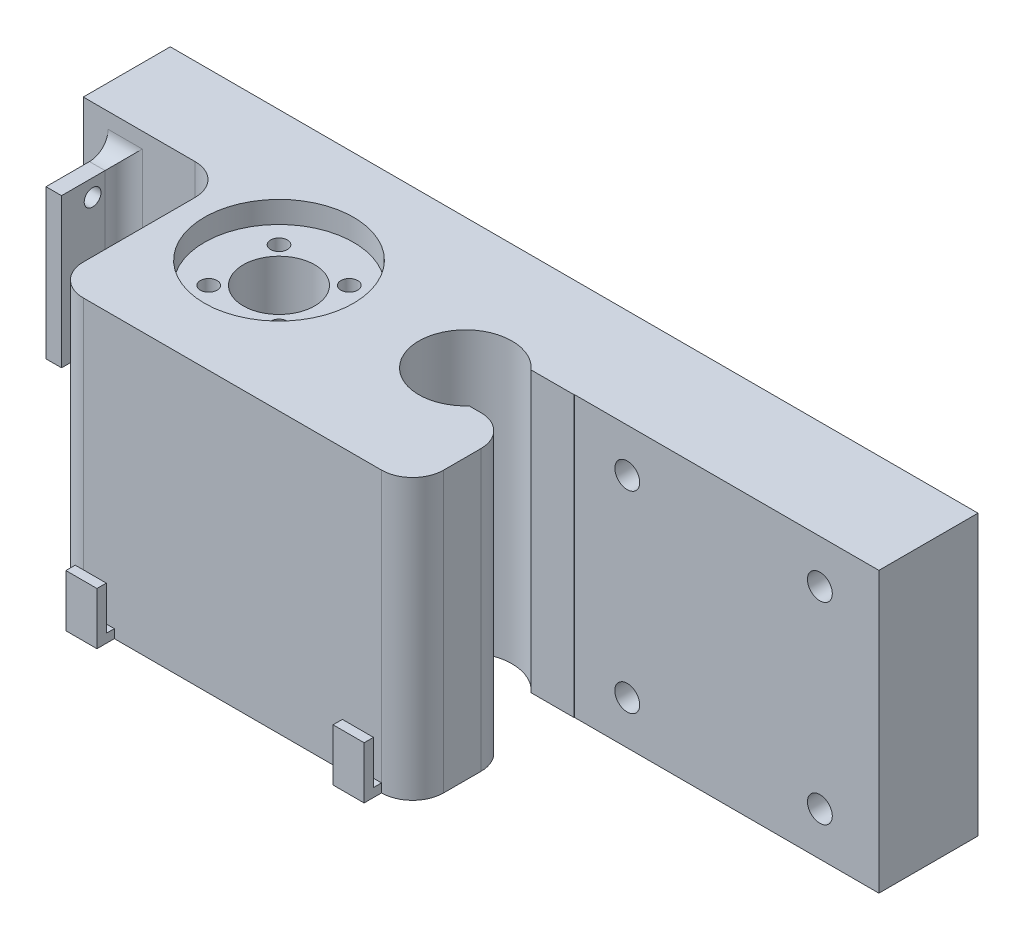
SolidWorks part; units mm, degrees
ref_plane "Front Plane" through (0, 0, 0) normal (0, 0, 1) x (1, 0, 0)
ref_plane "Top Plane" through (0, 0, 0) normal (0, 1, 0) x (1, 0, 0)
ref_plane "Right Plane" through (0, 0, 0) normal (1, 0, 0) x (0, 0, -1)
sketch "Sketch1" plane through (0, 0, 0) normal (0, 0, 1) x (1, 0, 0)
  line L1 (0, 0) -> (130, 0)
  line L2 (0, 0) -> (0, 45)
  line L3 (0, 45) -> (130, 45)
  line L4 (130, 0) -> (130, 45)
  dimension "D1" = 45
  dimension "D2" = 130
extrude "Boss-Extrude1" add sketch "Sketch1" along normal blind 42
sketch "Sketch2" plane through (0, 0, 0) normal (-1, 0, 0) x (0, 0, 1)
  line L0 (42, 22.5) -> (0, 22.5) construction
  line L5 (42, 45) -> (42, 0) construction
  line L6 (0, 45) -> (0, 0) construction
  line L8 (2, 12.5) -> (12, 12.5)
  line L9 (2, 12.5) -> (2, 32.5)
  line L10 (2, 32.5) -> (12, 32.5)
  line L11 (12, 12.5) -> (12, 32.5)
  line L12 (2, 12.5) -> (12, 32.5) construction
  line L13 (2, 32.5) -> (12, 12.5) construction
  point P10 (7, 22.5)
  dimension "D1" = 2
  dimension "D2" = 20
  dimension "D3" = 10
extrude "Cut-Extrude1" cut sketch "Sketch2" against normal blind 115
sketch "Sketch3" plane through (0, 0, 0) normal (0, 0, -1) x (-1, 0, 0)
  line L1 (-120.5, 38) -> (-89.5, 38) construction
  line L2 (-120.5, 38) -> (-120.5, 7) construction
  line L3 (-120.5, 7) -> (-89.5, 7) construction
  line L4 (-89.5, 38) -> (-89.5, 7) construction
  line L5 (-120.5, 38) -> (-89.5, 7) construction
  line L6 (-120.5, 7) -> (-89.5, 38) construction
  line L7 (-125.5, 43) -> (-84.5, 43)
  line L8 (-125.5, 43) -> (-125.5, 2)
  line L9 (-125.5, 2) -> (-84.5, 2)
  line L10 (-84.5, 43) -> (-84.5, 2)
  line L11 (-125.5, 43) -> (-84.5, 2) construction
  line L12 (-125.5, 2) -> (-84.5, 43) construction
  point P4 (-105, 22.5)
  point P11 (-105, 22.5)
  dimension "D1" = 5
  dimension "D2" = 5
extrude "Cut-Extrude2" cut sketch "Sketch3" against normal blind 12
sketch "Sketch5" plane through (0, 0, 42) normal (0, 0, 1) x (1, 0, 0)
  line L0 (0, 0) -> (130, 0) construction
  line L1 (130, 45) -> (81, 45)
  line L2 (130, 45) -> (130, 0)
  line L3 (130, 0) -> (81, 0)
  line L4 (81, 45) -> (81, 0)
  line L5 (130, 45) -> (81, 0) construction
  line L6 (130, 0) -> (81, 45) construction
  point P4 (105.5, 22.5)
  dimension "D1" = 49
extrude "Cut-Extrude3" cut sketch "Sketch5" against normal up to surface (26.05 mm away)
sketch "Sketch6" plane through (0, 0, 0) normal (0, 0, -1) x (-1, 0, 0)
  line L1 (-120.5, 38) -> (-89.5, 38) construction
  line L2 (-120.5, 38) -> (-120.5, 7) construction
  line L3 (-120.5, 7) -> (-89.5, 7) construction
  line L4 (-89.5, 38) -> (-89.5, 7) construction
  line L5 (-120.5, 38) -> (-89.5, 7) construction
  line L6 (-120.5, 7) -> (-89.5, 38) construction
  circle A0 centre (-120.5, 38) radius 2
  circle A1 centre (-89.5, 38) radius 2
  circle A2 centre (-89.5, 7) radius 2
  circle A3 centre (-120.5, 7) radius 2
  point P4 (-105, 22.5)
  dimension "D1" = 4
  dimension "D2" = 4
  dimension "D3" = 4
  dimension "D4" = 4
extrude "Cut-Extrude4" cut sketch "Sketch6" against normal through all
sketch "Sketch7" plane through (0, 45, 0) normal (0, 1, 0) x (1, 0, 0)
  circle A0 centre (38.5, -21) radius 12
  dimension "D1" = 24
extrude "Cut-Extrude5" cut sketch "Sketch7" against normal blind 3.5
sketch "Sketch8" plane through (0, 45, 0) normal (0, 1, 0) x (1, 0, 0)
  circle A0 centre (68.5, -21) radius 7.5
  dimension "D1" = 15
extrude "Cut-Extrude6" cut sketch "Sketch8" against normal through all
sketch "Sketch10" plane through (0, 45, 0) normal (0, 1, 0) x (1, 0, 0)
  line L1 (0, -42) -> (23, -42)
  line L2 (0, -42) -> (0, -14)
  line L3 (0, -14) -> (23, -14)
  line L4 (23, -42) -> (23, -14)
  line L5 (0, -42) -> (23, -14) construction
  line L6 (0, -14) -> (23, -42) construction
  point P4 (11.5, -28)
  dimension "D1" = 28
  dimension "D2" = 23
extrude "Cut-Extrude7" cut sketch "Sketch10" against normal through all
fillet "Fillet1" radius 5 2 edges at (23, 22.5, 42) (81, 22.5, 42)
sketch "Sketch11" plane through (0, 41.5, 0) normal (0, 1, 0) x (1, 0, 0)
  circle A0 centre (38.5, -21) radius 5.75
  dimension "D1" = 11.5
extrude "Cut-Extrude8" cut sketch "Sketch11" against normal through all
sketch "Sketch12" plane through (0, 41.5, 0) normal (0, 1, 0) x (1, 0, 0)
  circle A0 centre (32.8431, -15.3431) radius 1.35
  circle A1 centre (44.1569, -15.3431) radius 1.35
  circle A2 centre (44.1569, -26.6569) radius 1.35
  circle A3 centre (32.8431, -26.6569) radius 1.35
  dimension "D1" = 2.7
extrude "Cut-Extrude9" cut sketch "Sketch12" against normal blind 20
sketch "Sketch14" plane through (0, 0, 0) normal (0, 0, -1) x (-1, 0, 0)
  line L0 (0, 22.5) -> (-84.5, 22.5) construction
  line L1 (-75, 7.5) -> (-15, 7.5) construction
  line L2 (-75, 7.5) -> (-75, 37.5) construction
  line L3 (-75, 37.5) -> (-15, 37.5) construction
  line L4 (-15, 7.5) -> (-15, 37.5) construction
  line L5 (-75, 7.5) -> (-15, 37.5) construction
  line L6 (-75, 37.5) -> (-15, 7.5) construction
  line L7 (0, 45) -> (0, 0) construction
  line L8 (-84.5, 2) -> (-84.5, 43) construction
  circle A0 centre (-75, 37.5) radius 1.75
  circle A1 centre (-15, 37.5) radius 1.75
  circle A2 centre (-15, 7.5) radius 1.75
  circle A3 centre (-75, 7.5) radius 1.75
  point P0 (-45, 22.5)
  dimension "D4" = 3.5
  dimension "D1" = 60
  dimension "D2" = 30
  dimension "D3" = 15
extrude "Cut-Extrude11" cut sketch "Sketch14" against normal blind 12
sketch "Sketch15" plane through (0, 45, 0) normal (0, 1, 0) x (1, 0, 0)
  line L0 (61, -21) -> (86.2394, -21) construction
  line L2 (98.575, -16) -> (66.113, -16)
  line L3 (98.575, -16) -> (98.575, -26)
  line L4 (98.575, -26) -> (66.113, -26)
  line L5 (66.113, -16) -> (66.113, -26)
  line L6 (98.575, -16) -> (66.113, -26) construction
  line L7 (98.575, -26) -> (66.113, -16) construction
  circle A0 centre (68.5, -21) radius 7.5 construction
  point P5 (82.344, -21)
  dimension "D1" = 10
extrude "Cut-Extrude12" cut sketch "Sketch15" against normal through all
fillet "Fillet2" radius 5 1 edges at (81, 22.5, 26)
fillet "Fillet3" radius 5 1 edges at (23, 22.5, 14)
sketch "Sketch16" plane through (0, 0, 0) normal (0, -1, 0) x (1, 0, 0)
  circle A0 centre (38.5, 21) radius 12.5
  dimension "D1" = 25
extrude "Cut-Extrude13" cut sketch "Sketch16" against normal up to surface (32.5 mm away) up to face at (42.25, 32.5, 7)
sketch "Sketch17" plane through (0, 0, 14) normal (0, 0, 1) x (1, 0, 0)
  line L1 (4, 39.5) -> (6.5, 39.5)
  line L2 (4, 39.5) -> (4, 15.5)
  line L3 (4, 15.5) -> (6.5, 15.5)
  line L4 (6.5, 39.5) -> (6.5, 15.5)
  line L5 (4, 39.5) -> (6.5, 15.5) construction
  line L6 (4, 15.5) -> (6.5, 39.5) construction
  point P4 (5.25, 27.5)
  dimension "D1" = 24
  dimension "D2" = 2.5
extrude "Boss-Extrude2" add sketch "Sketch17" along normal blind 10
sketch "Sketch18" plane through (4, 0, 0) normal (-1, 0, 0) x (0, 0, 1)
  circle A0 centre (19, 36.775) radius 1.35
  circle A1 centre (19, 17.725) radius 1.35
  dimension "D1" = 2.7
extrude "Cut-Extrude14" cut sketch "Sketch18" against normal blind 10
fillet "Fillet4" radius 3 1 edges at (6.5, 27.5, 14)
fillet "Fillet5" radius 3 2 edges at (6.75, 39.5, 14) (6.75, 15.5, 14)
sketch "Sketch20" plane through (0, 0, 42) normal (0, 0, 1) x (1, 0, 0)
  line L1 (28, 0) -> (33, 0)
  line L2 (28, 0) -> (28, 1.4)
  line L3 (28, 1.4) -> (33, 1.4)
  line L4 (33, 0) -> (33, 1.4)
  line L5 (28, 0) -> (33, 1.4) construction
  line L6 (28, 1.4) -> (33, 0) construction
  line L7 (76, 0) -> (71, 0)
  line L8 (76, 0) -> (76, 1.4)
  line L9 (76, 1.4) -> (71, 1.4)
  line L10 (71, 0) -> (71, 1.4)
  line L11 (76, 0) -> (71, 1.4) construction
  line L12 (76, 1.4) -> (71, 0) construction
  point P4 (30.5, 0.7)
  point P10 (73.5, 0.7)
  dimension "D1" = 1.4
  dimension "D2" = 5
  dimension "D3" = 5
  dimension "D4" = 1.4
extrude "Boss-Extrude3" add sketch "Sketch20" along normal blind 2.8
sketch "Sketch22" plane through (23, 0, 0) normal (-1, 0, 0) x (0, 0, 1)
  line L0 (28, 45) -> (28, 0) construction
  line L1 (25.5, 0) -> (30.5, 0)
  line L2 (25.5, 0) -> (25.5, 1.4)
  line L3 (25.5, 1.4) -> (30.5, 1.4)
  line L4 (30.5, 0) -> (30.5, 1.4)
  line L5 (25.5, 0) -> (30.5, 1.4) construction
  line L6 (25.5, 1.4) -> (30.5, 0) construction
  line L7 (37, 45) -> (19, 45) construction
  line L8 (37, 0) -> (19, 0) construction
  point P4 (28, 0.7)
  point P12 (0, 0)
  dimension "D1" = 1.4
  dimension "D2" = 5
extrude "Boss-Extrude4" add sketch "Sketch22" along normal blind 2.8
sketch "Sketch25" plane through (0, 1.4, 0) normal (0, 1, 0) x (1, 0, 0)
  line L0 (20.2, -25.5) -> (23, -25.5) construction
  line L1 (20.2, -25.5) -> (21.7, -25.5)
  line L2 (20.2, -25.5) -> (20.2, -30.5)
  line L3 (20.2, -30.5) -> (21.7, -30.5)
  line L4 (21.7, -25.5) -> (21.7, -30.5)
  line L5 (20.2, -25.5) -> (21.7, -30.5) construction
  line L6 (20.2, -30.5) -> (21.7, -25.5) construction
  line L7 (20.2, -30.5) -> (23, -30.5) construction
  line L8 (23, -37) -> (23, -19) construction
  line L9 (76, -44.8) -> (76, -42) construction
  line L10 (76, -43.3) -> (71, -43.3)
  line L11 (76, -43.3) -> (76, -44.8)
  line L12 (76, -44.8) -> (71, -44.8)
  line L13 (71, -43.3) -> (71, -44.8)
  line L14 (76, -43.3) -> (71, -44.8) construction
  line L15 (76, -44.8) -> (71, -43.3) construction
  line L16 (71, -44.8) -> (71, -42) construction
  line L17 (33, -44.8) -> (33, -42) construction
  line L18 (33, -43.3) -> (28, -43.3)
  line L19 (33, -43.3) -> (33, -44.8)
  line L20 (33, -44.8) -> (28, -44.8)
  line L21 (28, -43.3) -> (28, -44.8)
  line L22 (33, -43.3) -> (28, -44.8) construction
  line L23 (33, -44.8) -> (28, -43.3) construction
  line L24 (28, -44.8) -> (28, -42) construction
  line L25 (76, -42) -> (71, -42) construction
  line L26 (33, -42) -> (28, -42) construction
  point P4 (20.95, -28)
  point P15 (73.5, -44.05)
  point P24 (30.5, -44.05)
  dimension "D1" = 1.3
  dimension "D2" = 1.5
  dimension "D3" = 1.5
  dimension "D4" = 1.3
  dimension "D5" = 1.5
  dimension "D6" = 1.3
extrude "Boss-Extrude5" add sketch "Sketch25" along normal blind 7
